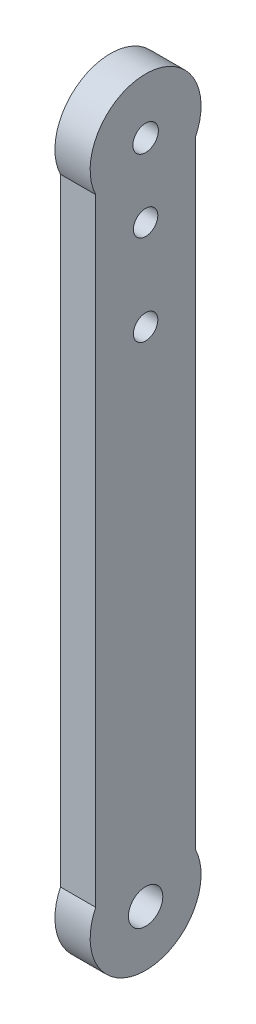
SolidWorks part; units mm, degrees
ref_plane "Front Plane" through (0, 0, 0) normal (0, 0, 1) x (1, 0, 0)
ref_plane "Top Plane" through (0, 0, 0) normal (0, 1, 0) x (1, 0, 0)
ref_plane "Right Plane" through (0, 0, 0) normal (1, 0, 0) x (0, 0, -1)
sketch "Sketch1" plane through (0, 0, 0) normal (1, 0, 0) x (0, 0, -1)
  line L0 (0, 0) -> (-4.5, -2.1794) construction
  line L2 (4.5, -2.1794) -> (4.5, -57.8206)
  line L3 (4.5, -57.8206) -> (-4.5, -57.8206) construction
  line L4 (-4.5, -2.1794) -> (-4.5, -57.8206)
  line L5 (4.5, -2.1794) -> (-4.5, -2.1794) construction
  line L6 (0, 0) -> (4.5, -2.1794) construction
  arc A1 (4.5, -2.1794) -> (-4.5, -2.1794) centre (0, 0) ccw
  arc A2 (-4.5, -57.8206) -> (4.5, -57.8206) centre (0, -60) ccw
  circle A3 centre (0, -60) radius 1.55
  circle A24 centre (0, -14.75) radius 1.1
  circle A264 centre (0, 0) radius 1.15
  circle A265 centre (0, -6.6) radius 1.1
  dimension "D1" = 2.3
  dimension "D2" = 10
  dimension "D4" = 10
  dimension "D6" = 3.1
  dimension "D7" = 2.2
  dimension "D3" = 9
  dimension "D5" = 60
  dimension "D8" = 8.15
  dimension "D9" = 6.6
extrude "Boss-Extrude3" add sketch "Sketch1" along normal blind 3.175
